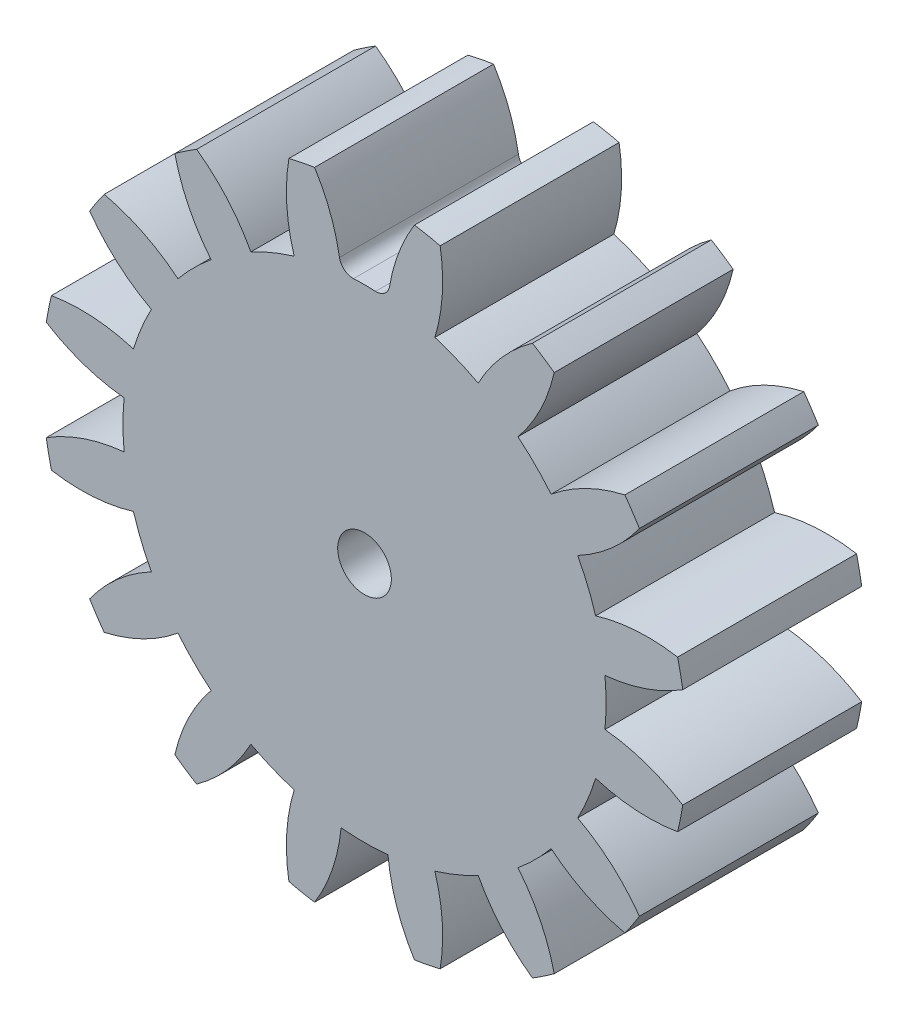
SolidWorks part; units mm, degrees
ref_plane "Front Plane" through (0, 0, 0) normal (0, 0, 1) x (1, 0, 0)
ref_plane "Top Plane" through (0, 0, 0) normal (0, 1, 0) x (1, 0, 0)
ref_plane "Right Plane" through (0, 0, 0) normal (1, 0, 0) x (0, 0, -1)
sketch "Sketch1" plane through (0, 0, 0) normal (0, 0, 1) x (1, 0, 0)
  circle A0 centre (0, 0) radius 18
  circle A1 centre (0, 0) radius 1.5
  dimension "D1" = 3
  dimension "D2" = 36
extrude "Boss-Extrude1" add sketch "Sketch1" along normal mid plane 10
sketch "Sketch2" plane through (0, 0, 0) normal (0, 0, 1) x (1, 0, 0)
  line L0 (0, 0) -> (0, 18) construction
  line L1 (0, 0) -> (-1.3096, 13.4363) construction
  line L2 (0, 10.7625) -> (-3.5688, 20.5678) construction
  arc A0 (1.8665, 15.8908) -> (-1.8665, 15.8908) centre (0, 0) ccw construction
  arc A1 (1.3096, 13.4363) -> (-1.3096, 13.4363) centre (0, 0) ccw
  circle A2 centre (0, 0) radius 18 construction
  arc A3 (2.7904, 17.7824) -> (-2.7904, 17.7824) centre (0, 0) ccw
  arc A4 (-1.3096, 13.4363) -> (-2.7904, 17.7824) centre (-11.2801, 12.4645) ccw
  arc A5 (1.3096, 13.4363) -> (2.7904, 17.7824) centre (11.2801, 12.4645) cw
  dimension "D1" = 32
  dimension "D2" = 4.5
  dimension "D3" = 20
  dimension "D4" = 3.7416
extrude "Cut-Extrude1" cut sketch "Sketch2" against normal through all both and the other way through all
fillet "Fillet1" radius 0.76 2 edges at (1.3096, 13.4363, 0) (-1.3096, 13.4363, 0)
pattern_circular "CirPattern3" count 16 over 360 about axis through (0, 0, 5) along (0, 0, -1) of "Cut-Extrude1"
equation "\"Module\" = 02"
equation "\"Pressure Angle\"= 20"
equation "\"Bore\"= 3"
equation "\"NumTeeth\" = 16"
equation "\"D1@Sketch1\"=\"Bore\""
equation "\"D2@Sketch1\"=(\"NumTeeth\"+2)*\"Module\""
equation "\"D1@Sketch2\"=\"NumTeeth\"*\"Module\""
equation "\"ToothDepth\"= IIF ( \"Module\" < 1.25 , 2.4 * \"Module\" , 2.25 * \"Module\" )"
equation "\"D2@Sketch2\"=\"ToothDepth\""
equation "\"D3@Sketch2\"=\"Pressure Angle\""
equation "\"D4@Sketch2\"=((\"Module\"*PI)/2)+0.3*\"Module\""
equation "\"D1@Fillet1\"=\"Module\"*0.38"
equation "\"D1@CirPattern3\"=\"NumTeeth\""
